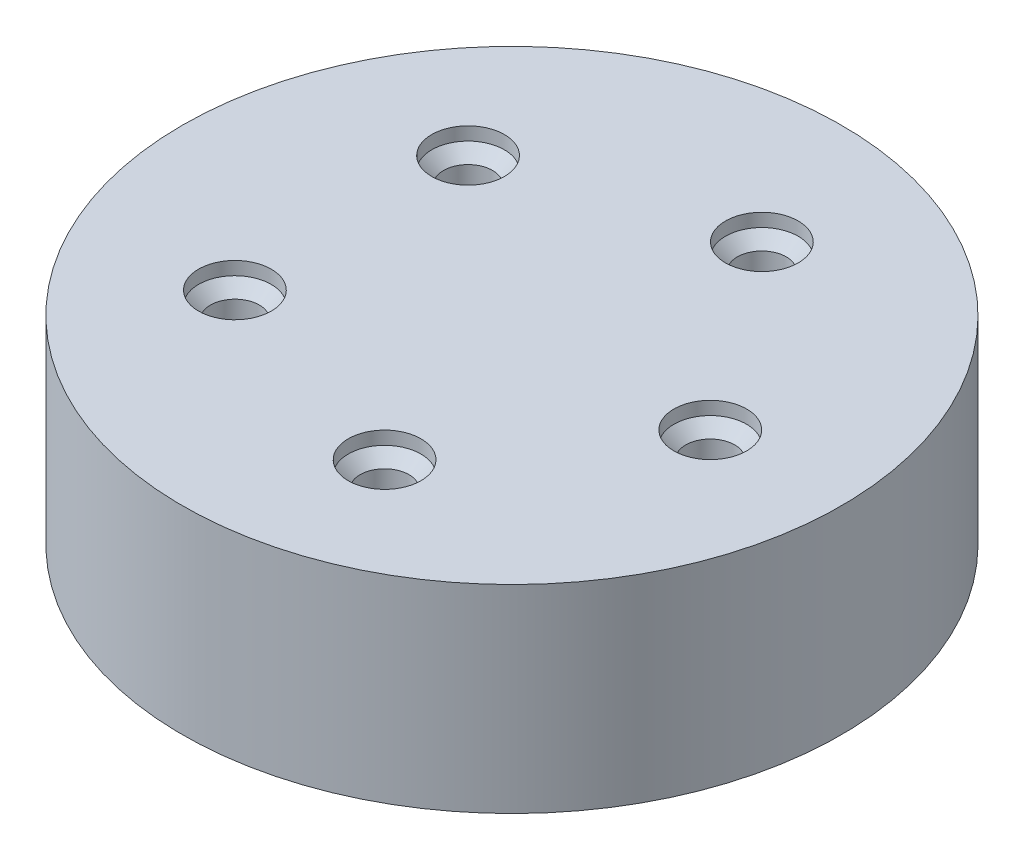
SolidWorks part; units mm, degrees
ref_plane "Front Plane" through (0, 0, 0) normal (0, 0, 1) x (1, 0, 0)
ref_plane "Top Plane" through (0, 0, 0) normal (0, 1, 0) x (1, 0, 0)
ref_plane "Right Plane" through (0, 0, 0) normal (1, 0, 0) x (0, 0, -1)
sketch "Sketch3" plane through (0, 15, 0) normal (0, 1, 0) x (1, 0, 0)
  circle A0 centre (-1.2, 0) radius 24.925
  circle A1 centre (13.8, 0) radius 1.85
  circle A6 centre (-1.2, 0) radius 15
  circle A7 centre (-1.2, 0) radius 15
  circle A8 centre (3.4353, -14.2658) radius 1.85
  circle A9 centre (-1.2, 0) radius 15
  circle A10 centre (-13.3353, -8.8168) radius 1.85
  circle A11 centre (-1.2, 0) radius 15
  circle A12 centre (-13.3353, 8.8168) radius 1.85
  circle A13 centre (-1.2, 0) radius 15
  circle A14 centre (3.4353, 14.2658) radius 1.85
  dimension "D1" = 49.85
  dimension "D2" = 5
  dimension "D3" = 3.7
extrude "Boss-Extrude1" add sketch "Sketch3" along normal blind 5 and the other way blind 10 contours A14 A6 A12 A10 A8 A1 | A0 A14 A6 A1 A8 A10 A12 region at (-25.42, 15, 0) region at (-1.2, 15, 0)
sketch "Sketch4" plane through (0, 20, 0) normal (0, 1, 0) x (1, 0, 0)
  circle A0 centre (-1.2, 0) radius 15
  circle A1 centre (13.8, 0) radius 1.85
  circle A2 centre (3.4353, -14.2658) radius 1.85
  circle A3 centre (-13.3353, -8.8168) radius 1.85
  circle A4 centre (-13.3353, 8.8168) radius 1.85
  circle A5 centre (3.4353, 14.2658) radius 1.85
  point P4 (13.8, 0)
  point P8 (3.4353, -14.2658)
  point P10 (-13.3353, -8.8168)
  point P12 (-13.3353, 8.8168)
  point P14 (3.4353, 14.2658)
  dimension "D1" = 5
hole_wizard "CSK for M2.5 Flat Head Machine Screw1" positions "Sketch4" profile "Sketch5" countersink size "M2.5" standard "ANSI Metric" end condition through all
sketch "Sketch5" plane through (3.4353, 20, -14.2658) normal (1, 0, 0) x (0, 0, 1)
  line L0 (0, 0) -> (0, 15)
  line L1 (0, 15) -> (1.45, 15)
  line L2 (1.45, 15) -> (1.45, 2.3)
  line L3 (1.45, 2.3) -> (2.75, 1)
  line L4 (2.75, 1) -> (2.75, 0)
  line L6 (2.75, 0) -> (0, 0)
  line L7 (-1.45, 2.3) -> (-2.75, 1) construction
  line L11 (0, -6.35) -> (0, 107.95) construction
  dimension "Thru Hole Dia." = 2.9
  dimension "Thru Hole Depth" = 15
  dimension "C'Sink Dia." = 5.5
  dimension "C'Sink Angle" = 90
  dimension "Head Clearance" = 1
